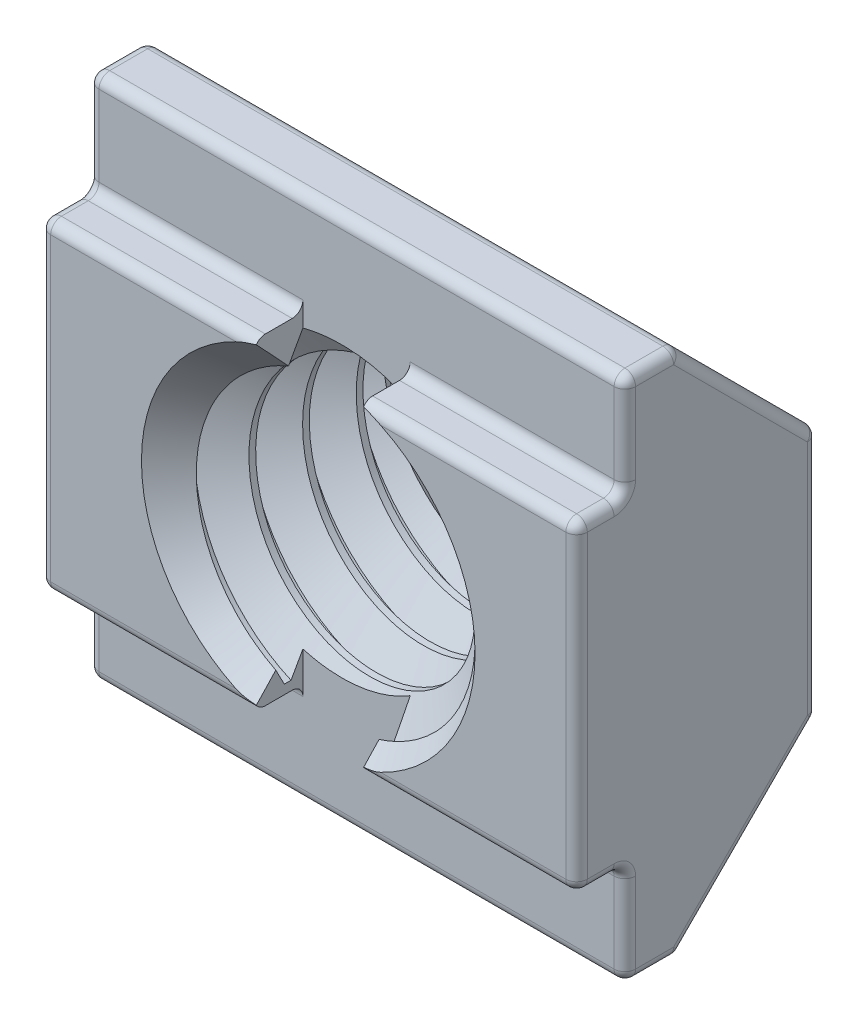
SolidWorks part; units mm, degrees
ref_plane "Front Plane" through (0, 0, 0) normal (0, 0, 1) x (1, 0, 0)
ref_plane "Top Plane" through (0, 0, 0) normal (0, 1, 0) x (1, 0, 0)
ref_plane "Right Plane" through (0, 0, 0) normal (1, 0, 0) x (0, 0, -1)
sketch "Sketch1" plane through (0, 0, 0) normal (0, 0, 1) x (1, 0, 0)
  line L0 (0, 4.9) -> (0, -4.9) construction
  line L1 (-5, 4.9) -> (5, 4.9) construction
  line L2 (-5, 4.9) -> (-5, -4.9) construction
  line L3 (-5, -4.9) -> (5, -4.9) construction
  line L4 (5, 4.9) -> (5, -4.9) construction
  line L5 (-5, 0) -> (5, 0) construction
  circle A1 centre (0, 0) radius 3 construction
  point P5 (0, 0)
  point P12 (0, -3)
  point P14 (0, 3)
  dimension "Thread Diameter" = 6
  dimension "Length" = 10
  dimension "Width" = 9.8
  dimension "D3" = 5
sketch "Sketch2" plane through (0, 0, 0) normal (1, 0, 0) x (0, 0, -1)
  line L0 (-2.25, 0) -> (2.25, 0) construction
  line L1 (-3.1875, 3.1083) -> (-2.6875, 2.2422)
  line L2 (-2.25, 3) -> (-2.25, -3) construction
  line L3 (-2.6875, 2.2422) -> (-2.1875, 3.1083)
  line L4 (-2.1875, 3.1083) -> (-3.1875, 3.1083)
  line L5 (-2.6875, 3.1083) -> (-2.6875, 3)
  line L6 (-2.6875, 2.2422) -> (-2.6875, 2.3505)
  line L7 (-3.125, 3) -> (-2.25, 3)
  line L8 (-3.1562, 3.0541) -> (-2.2188, 3.0541)
  line L9 (-2.75, 2.3505) -> (-2.625, 2.3505)
  point P3 (0, 0)
  point P6 (-2.25, 0)
  point P7 (-1.35, 0)
  point P9 (-2.25, -3)
  point P11 (-2.25, 3)
  point P22 (-2.6875, 3)
  point P25 (-2.6875, 3.0541)
  point P28 (-2.6875, 2.3505)
  dimension "D1" = 6
  dimension "D2" = 0.9
  dimension "Thickness" = 4.5
  dimension "Thread Pitch" = 1
  dimension "D6" = 0.125
sketch "Sketch3" plane through (0, 0, 0) normal (1, 0, 0) x (0, 0, -1)
  line L0 (-2.25, 3) -> (-1.35, 3)
  line L1 (-1.35, 3) -> (-1.35, 4.9)
  line L3 (-2.25, -3) -> (-1.35, -3)
  line L4 (-1.35, -3) -> (-1.35, -4.9)
  line L9 (-1.35, 4.9) -> (-0.36, 4.9)
  line L10 (-0.36, 4.9) -> (2.25, 2.29)
  line L11 (2.25, 2.29) -> (2.25, -2.29)
  line L12 (2.25, -2.29) -> (-0.36, -4.9)
  line L13 (-0.36, -4.9) -> (-1.35, -4.9)
  line L14 (-2.25, 3) -> (-2.25, -3)
  line L15 (-2.25, 0) -> (2.25, 0) construction
  point P16 (2.25, 0)
  dimension "D4" = 2.61
  dimension "D3" = 45
extrude "Boss-Extrude1" add sketch "Sketch3" against normal up to vertex (5 mm away) and the other way up to vertex (5 mm away) up to point (-5, 0, 0) other way up to point (5, 4.9, 0)
fillet "Fillet4" radius 0.2 10 edges at (0, -3, 2.25) (0, -3, 1.35) (0, -4.9, 1.35) (0, -4.9, 0.36) (0, -2.29, -2.25) (0, 2.29, -2.25) (0, 4.9, 0.36) (0, 4.9, 1.35) (0, 3, 1.35) (0, 3, 2.25)
sketch "Sketch19" plane through (0, 0, 2.25) normal (0, 0, 1) x (1, 0, 0)
  line L1 (-1, 4.9) -> (1, 4.9)
  line L2 (-1, 4.9) -> (-1, -4.9)
  line L3 (-1, -4.9) -> (1, -4.9)
  line L4 (1, 4.9) -> (1, -4.9)
  dimension "D1" = 2
extrude "Cut-Extrude11" cut sketch "Sketch19" against normal up to surface (0.9 mm away) up to face at (0, 3.95, 1.35)
sketch "Sketch6" plane through (0, 0, 2.25) normal (0, 0, 1) x (1, 0, 0)
  circle A0 centre (0, 0) radius 3 construction
  circle A1 centre (0, 0) radius 3
extrude "Cut-Extrude2" cut sketch "Sketch6" against normal through all
fillet "Fillet5" radius 0.2 40 edges at (-5, 2.9414, 2.1914) (-5, 3, 1.8) (-5, 3.0586, 1.4086) (-5, 3.95, 1.35) (-5, 4.8414, 1.2914) (-5, 4.9, 0.7964) (-5, 4.8848, 0.3663) (-5, 3.595, -0.945) (-5, 2.2837, -2.2348) (-5, 0, -2.25) (-5, -2.2837, -2.2348) (-5, -3.595, -0.945) (-5, -4.8848, 0.3663) (-5, -4.9, 0.7964) (-5, -4.8414, 1.2914) (-5, -3.95, 1.35) (-5, -3.0586, 1.4086) (-5, -3, 1.8) (-5, -2.9414, 2.1914) (5, 2.9414, 2.1914) (5, 3, 1.8) (5, 3.0586, 1.4086) (5, 3.95, 1.35) (5, 4.8414, 1.2914) (5, 4.9, 0.7964) (5, 4.8848, 0.3663) (5, 3.595, -0.945) (5, 2.2837, -2.2348) (5, 0, -2.25) (5, -2.2837, -2.2348) (5, -3.595, -0.945) (5, -4.8848, 0.3663) (5, -4.9, 0.7964) (5, -4.8414, 1.2914) (5, -3.95, 1.35) (5, -3.0586, 1.4086) (5, -3, 1.8) (5, -2.9414, 2.1914) (-5, 0, 2.25) (5, 0, 2.25)
sketch "Sketch8" plane through (0, 0, 0) normal (0, 0, 1) x (1, 0, 0)
  line L0 (0, 0) -> (2.1213, -2.1213)
  line L1 (-5, 0) -> (5, 0) construction
  circle A0 centre (0, 0) radius 3 construction
  circle A1 centre (0, 0) radius 3
  point P0 (-5, 4.9)
  point P1 (5, 4.9)
  point P3 (-5, -4.9)
  point P13 (2.1213, -2.1213)
  dimension "D1" = 45
sketch "Sketch9" plane through (0, 0, 0) normal (1, 0, 0) x (0, 0, -1)
  line L0 (2.25, 2.2072) -> (2.25, -2.2072) construction
  line L2 (2.25, 2.2072) -> (2.25, -2.2072)
  point P0 (-2.25, 3)
  point P1 (2.25, 2.2072)
  point P2 (-2.25, -3)
  point P7 (2.25, -2.2072)
ref_plane "Plane2" through (0, 0, 0) normal (1, 0, 0) x (0, 0, -1)
sketch "Sketch10" plane through (0, 0, 2.25) normal (0, 0, 1) x (1, 0, 0)
  circle A0 centre (0, 0) radius 3 construction
  circle A1 centre (0, 0) radius 3
curve "Helix/Spiral1" pitch 1 height 5.5 radius 3 centre (0, 0, 2.25) axis (0, 0, -1) start towards (0, 1, 0)
sketch "Sketch11" plane through (0, 0, 0) normal (1, 0, 0) x (0, 0, -1)
  line L0 (-2.75, 2.3505) -> (-2.625, 2.3505) construction
  line L1 (-2.6875, 2.2422) -> (-2.1875, 3.1083) construction
  line L2 (-3.1875, 3.1083) -> (-2.6875, 2.2422) construction
  line L3 (-3.1562, 3.0541) -> (-2.2188, 3.0541) construction
  line L4 (-2.75, 2.3505) -> (-2.625, 2.3505)
  line L5 (-2.625, 2.3505) -> (-2.2188, 3.0541)
  line L6 (-3.1562, 3.0541) -> (-2.75, 2.3505)
  line L7 (-3.1562, 3.0541) -> (-2.2188, 3.0541)
sweep "Sweep1" add profiles "Sketch11" path "Helix/Spiral1"
sketch "Sketch20" plane through (0, 0, 2.25) normal (0, 0, 1) x (1, 0, 0)
  line L4 (1, 4.9) -> (-1, 4.9)
  line L5 (1, -4.9) -> (1, 4.9)
  line L6 (-1, -4.9) -> (1, -4.9)
  line L7 (-1, 4.9) -> (-1, -4.9)
  line L8 (1, 4.9) -> (-1, 4.9)
  line L9 (1, -4.9) -> (1, 4.9)
  line L10 (-1, -4.9) -> (1, -4.9)
  line L11 (-1, 4.9) -> (-1, -4.9)
  dimension "D1" = 0
extrude "Cut-Extrude12" cut sketch "Sketch20" against normal up to surface (0.9 mm away) and the other way through all up to face at (0.0322, 3.5161, 1.35)
sketch "Sketch17" plane through (0, 0, 2.25) normal (0, 0, 1) x (1, 0, 0)
  circle A0 centre (0, 0) radius 3.1083
extrude "Cut-Extrude9" cut sketch "Sketch17" against normal through all draft 45 and the other way through all
sketch "Sketch18" plane through (0, 0, -2.25) normal (0, 0, -1) x (-1, 0, 0)
  circle A1 centre (0, 0) radius 3.1083
  circle A2 centre (0, 0) radius 3.1083
  dimension "D1" = 0
extrude "Cut-Extrude10" cut sketch "Sketch18" against normal through all draft 45 and the other way through all
sketch "Sketch21" plane through (5, 0, 0) normal (1, 0, 0) x (0, 0, -1)
  line L0 (-0.36, -4.9) -> (2.25, -4.9)
  line L1 (2.25, -4.9) -> (2.25, -2.29)
  line L2 (2.25, 2.29) -> (2.25, 4.9)
  line L3 (2.25, 4.9) -> (-0.36, 4.9)
  line L10 (-1.35, 4.9) -> (-1.35, 3)
  line L11 (-1.35, 3) -> (-2.25, 3)
  line L12 (-2.25, 3) -> (-2.25, -3)
  line L13 (-2.25, -3) -> (-1.35, -3)
  line L14 (-1.35, -3) -> (-1.35, -4.9)
  line L15 (-1.35, -4.9) -> (-0.36, -4.9)
  line L16 (-0.36, -4.9) -> (2.25, -2.29)
  line L17 (2.25, -2.29) -> (2.25, 2.29)
  line L18 (2.25, 2.29) -> (-0.36, 4.9)
  line L19 (-0.36, 4.9) -> (-1.35, 4.9)
  line L26 (-0.36, -4.9) -> (2.25, -2.29)
  line L28 (2.25, 2.29) -> (-0.36, 4.9)
  dimension "D1" = 0
extrude "Cut-Extrude13" cut sketch "Sketch21" against normal through all
equation "\"D6@Sketch2\" = \"Thread Pitch@Sketch2\" / 8"
equation "\"D3@Helix/Spiral1\" = \"Thickness@Sketch2\" + \"Thread Pitch@Sketch2\""
equation "\"D4@Helix/Spiral1\" = \"Thread Pitch@Sketch2\""
equation "\"D3@Sketch1\"=\"Length@Sketch1\"/2"
